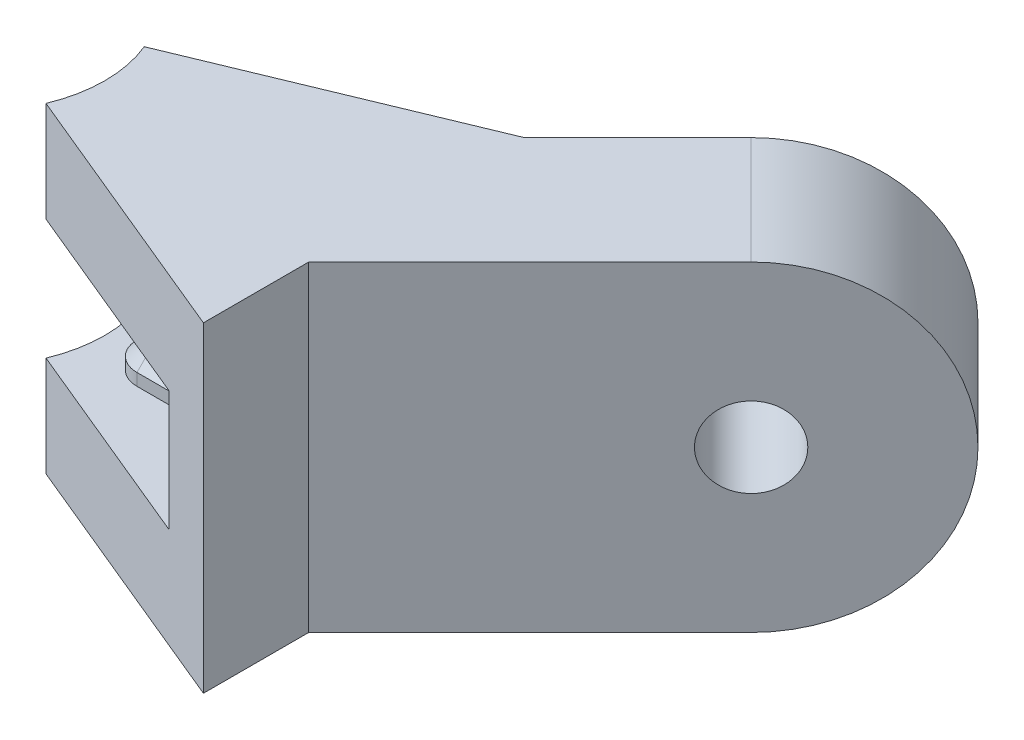
SolidWorks part; units mm, degrees
ref_plane "Ebene vorne" through (0, 0, 0) normal (0, 0, 1) x (1, 0, 0)
ref_plane "Ebene oben" through (0, 0, 0) normal (0, 1, 0) x (1, 0, 0)
ref_plane "Ebene rechts" through (0, 0, 0) normal (1, 0, 0) x (0, 0, -1)
sketch "Skizze1" plane through (0, 0, 0) normal (0, 1, 0) x (1, 0, 0)
  line L0 (2.9564, 1.2246) -> (9.6569, 4)
  line L1 (9.6569, 4) -> (9.6569, -4)
  line L2 (9.6569, -4) -> (2.9564, -1.2246)
  arc A0 (2.9564, -1.2246) -> (2.9564, 1.2246) centre (0, 0) ccw
  point P3 (9.6569, 0)
  dimension "D1" = 6.4
  dimension "D2" = 45
  dimension "D3" = 8
extrude "Aufsatz-Linear austragen1" add sketch "Skizze1" along normal mid plane 8
sketch "Skizze2" plane through (0, 0, 0) normal (0, 0, 1) x (1, 0, 0)
  line L5 (0, 1.5) -> (8.2, 1.5)
  line L6 (0, 1.5) -> (0, -1.5)
  line L7 (0, -1.5) -> (8.2, -1.5)
  line L8 (8.2, 1.5) -> (8.2, -1.5)
  point P4 (0, 0)
  dimension "D1" = 1.5
  dimension "D2" = 8.2
extrude "Schnitt-Linear austragen1" cut sketch "Skizze2" against normal through all both and the other way through all
sketch "Skizze7" plane through (0, 1.5, 0) normal (0, -1, 0) x (1, 0, 0)
  line L0 (4.7, 0) -> (5.5, 0) construction
  line L1 (4.7, 0.7) -> (5.5, 0.7)
  line L2 (4.7, -0.7) -> (5.5, -0.7)
  arc A0 (4.7, 0.7) -> (4.7, -0.7) centre (4.7, 0) ccw
  arc A1 (5.5, -0.7) -> (5.5, 0.7) centre (5.5, 0) ccw
  point P3 (5.1, 0)
  dimension "D1" = 4
  dimension "D2" = 6.2
  dimension "D3" = 1.4
extrude "Aufsatz-Linear austragen2" add sketch "Skizze7" along normal blind 0.6
chamfer "Fase1" distance 0.3 angle 45 4 edges at (5.1, 0.9, -0.7) (6.2, 0.9, 0) (4, 0.9, 0) (5.1, 0.9, 0.7)
mirror "Spiegeln1" about plane through (0, 0, 0) normal (0, 1, 0) of "Aufsatz-Linear austragen2", "Fase1"
sketch "Skizze13" plane through (0, 0, 0) normal (0, 1, 0) x (1, 0, 0)
  line L0 (9.6569, 4) -> (15.3137, 9.6569)
  line L1 (15.3137, 9.6569) -> (18.0007, 6.9698)
  line L2 (18.0007, 6.9698) -> (9.6569, -1.374)
  line L3 (9.6569, -4) -> (9.6569, 4) construction
  line L4 (9.6569, -1.374) -> (9.6569, 4)
  line L5 (0, 0) -> (9.6569, 0) construction
  dimension "D1" = 135
  dimension "D2" = 3.8
  dimension "D3" = 8
extrude "Aufsatz-Linear austragen5" add sketch "Skizze13" along normal up to surface and the other way up to surface up to face at (6.3675, 4, 0) other way up to face at (6.3675, -4, 0)
fillet "Verrundung2" radius 4 2 edges at (16.6572, -4, -8.3134) (16.6572, 4, -8.3134)
sketch "Skizze15" plane through (5.5154, 0, 5.5154) normal (0.7071, 0, 0.7071) x (0.7071, 0, -0.7071)
  circle A0 centre (13.6569, 0) radius 1
  arc A1 (17.6569, 0) -> (13.6569, 4) centre (13.6569, 0) ccw construction
  dimension "D1" = 2
extrude "Schnitt-Linear austragen2" cut sketch "Skizze15" against normal through all
